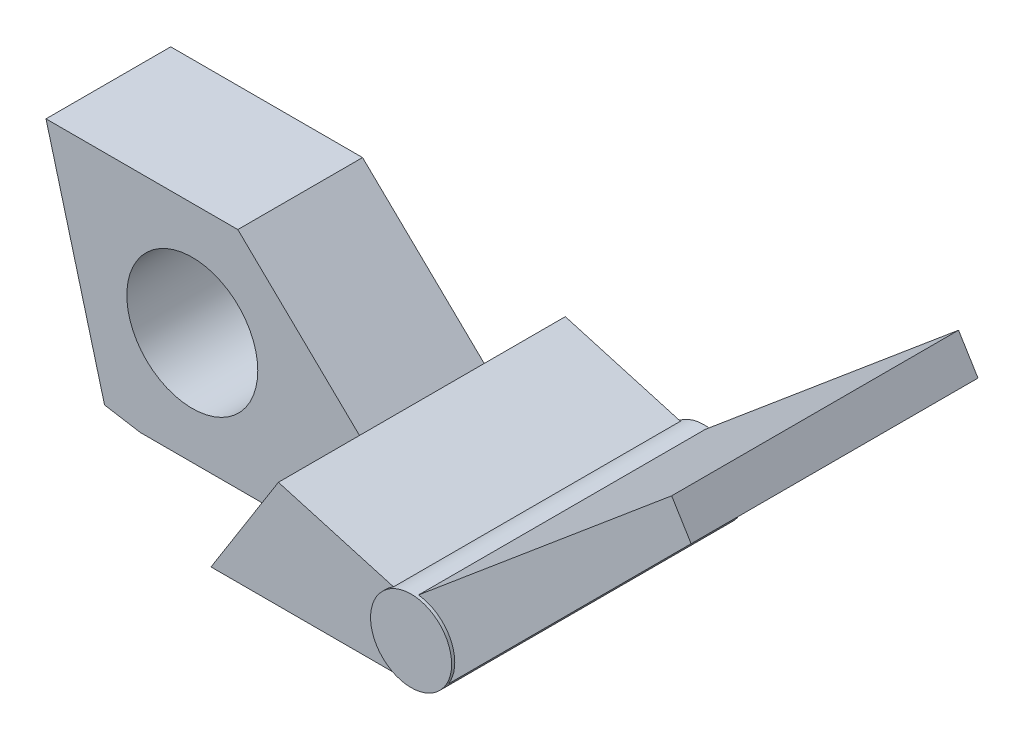
SolidWorks part; units mm, degrees
ref_plane "Front Plane" through (0, 0, 0) normal (0, 0, 1) x (1, 0, 0)
ref_plane "Top Plane" through (0, 0, 0) normal (0, 1, 0) x (1, 0, 0)
ref_plane "Right Plane" through (0, 0, 0) normal (1, 0, 0) x (0, 0, -1)
sketch "Sketch2" plane through (0, 0, 0) normal (0, 0, 1) x (1, 0, 0)
  line L0 (0, -9) -> (23.45, -9)
  line L1 (0, 9) -> (3.65, 9)
  line L2 (3.65, 9) -> (13.4042, -0.4196)
  line L3 (13.4042, -0.4196) -> (22.6342, -3.0662)
  line L4 (24.6325, -2.629) -> (44.9327, 14.4049)
  line L5 (27.0471, -7.5864) -> (46.4925, 11.8591)
  line L6 (46.4925, 11.8591) -> (44.9327, 14.4049)
  line L7 (13.4042, -0.4196) -> (8, -9)
  line L8 (13.4042, -0.4196) -> (8, -9)
  line L9 (22.6342, -3.0662) -> (13.4042, -0.4196)
  line L10 (8, -9) -> (23.45, -9)
  line L11 (0, 9) -> (-9, 9)
  line L12 (-9, 9) -> (-9, 0)
  line L13 (-9, 0) -> (-9, -9)
  line L14 (-9, -9) -> (0, -9)
  circle A0 centre (0, 0) radius 5.25
  circle A1 centre (0, 0) radius 9
  circle A4 centre (24.2928, -5.8612) radius 3.25
  circle A5 centre (24.2928, -5.8612) radius 3.25
  point P17 (8, -9)
  dimension "D1" = 10.5
  dimension "D2" = 18
  dimension "D9" = 24.2928
  dimension "D10" = 6.5
  dimension "D3" = 23.45
  dimension "D4" = 3.65
  dimension "D5" = 136
  dimension "D6" = 13.56
  dimension "D7" = 152
  dimension "D8" = 9.23
  dimension "D11" = 124
  dimension "D12" = 135
  dimension "D13" = 26.5
  dimension "D14" = 27.5
  dimension "D15" = 8
extrude "Boss-Extrude1" add sketch "Sketch2" along normal mid plane 10 contours A1 A0 | A1 L11 L12 | A1 L13 L14 | A1 L0 L7 L2 L1 region at (8.808, -2.8244, 0) region at (-6.9897, -6.9897, 0) region at (-6.184, -6.184, 0) region at (-6.9897, 6.9897, 0)
extrude "Boss-Extrude2" add sketch "Sketch2<15>" along normal mid plane 23 contours A4 L3 L7 L0 | A4 L5 L6 L4 region at (15.7342, -5.5199, 0) region at (35.3078, 3.589, 0)
sketch "Sketch2<15>" plane through (0, 0, 0) normal (0, 0, 1) x (1, 0, 0) same geometry as "Sketch2"
extrude "Boss-Extrude3" add sketch "Sketch2<16>" along normal mid plane 23.5 contours A4 region at (24.2928, -5.8612, 0)
sketch "Sketch2<16>" plane through (0, 0, 0) normal (0, 0, 1) x (1, 0, 0) same geometry as "Sketch2"
sketch "Sketch3" plane through (0, 0, -5) normal (0, 0, -1) x (-1, 0, 0)
  line L0 (9, 9) -> (9, -9)
  line L1 (9, -9) -> (4.1769, -9)
  line L2 (4.1769, -9) -> (9, 9)
  dimension "D1" = 15
extrude "Cut-Extrude1" cut sketch "Sketch3" against normal blind 10
sketch "Sketch4" plane through (0, 0, -5) normal (0, 0, -1) x (-1, 0, 0)
  line L0 (9, 9) -> (11.729, 9)
  line L1 (11.729, 9) -> (7.0339, -8.5226)
  line L2 (9, -9) -> (0, -9) construction
  line L3 (9, 9) -> (4.1769, -9) construction
  line L4 (7.0339, -8.5226) -> (4.1769, -9)
  line L5 (4.1769, -9) -> (9, 9)
  circle A0 centre (0, 0) radius 9 construction
extrude "Boss-Extrude4" add sketch "Sketch4" against normal blind 10
ref_plane "Plane1" through (-4.1769, -9, -5) normal (-0.9863, 0.1648, 0) x (0, 0, 1)
